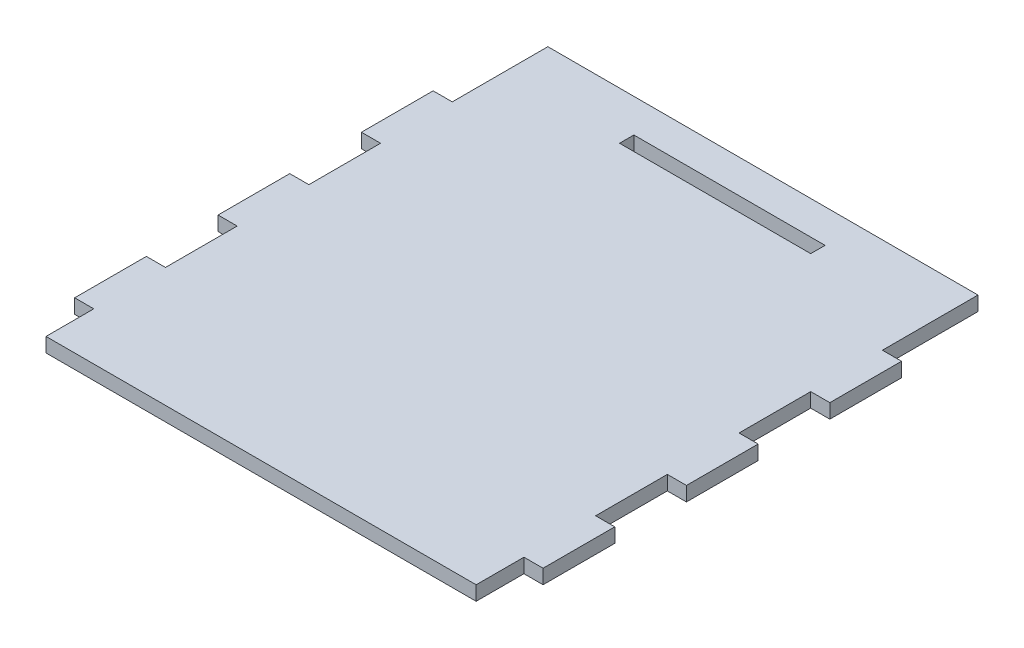
SolidWorks part; units mm, degrees
ref_plane "Front" through (0, 0, 0) normal (0, 0, 1) x (1, 0, 0)
ref_plane "Top" through (0, 0, 0) normal (0, 1, 0) x (1, 0, 0)
ref_plane "Right" through (0, 0, 0) normal (1, 0, 0) x (0, 0, -1)
sketch "Sketch1" plane through (0, 0, 0) normal (0, 1, 0) x (1, 0, 0)
  line L0 (0, 47.5) -> (90, 47.5) construction
  line L1 (0, 0) -> (90, 0)
  line L2 (0, 0) -> (0, 95)
  line L3 (0, 95) -> (90, 95)
  line L4 (90, 0) -> (90, 95)
  line L5 (45, 95) -> (45, 0) construction
  dimension "D1" = 90
  dimension "D7" = 95
extrude "Boss-Extrude1" add sketch "Sketch1" along normal blind 3
sketch "Sketch2" [suppressed] plane through (0, 3, 0) normal (0, 1, 0) x (1, 0, 0)
  line L1 (27.5, 98) -> (62.5, 98)
  line L2 (27.5, 98) -> (27.5, 95)
  line L3 (27.5, 95) -> (62.5, 95)
  line L4 (62.5, 98) -> (62.5, 95)
  dimension "D1" = 3
  dimension "D2" = 35
extrude "Boss-Extrude2" [suppressed] add sketch "Sketch2" against normal blind 3
sketch "Sketch3" [suppressed] plane through (0, 3, 0) normal (0, 1, 0) x (1, 0, 0)
  line L1 (-4, 67.5) -> (0, 67.5)
  line L2 (-4, 67.5) -> (-4, 27.5)
  line L3 (-4, 27.5) -> (0, 27.5)
  line L4 (0, 67.5) -> (0, 27.5)
  line L5 (90, 27.5) -> (94, 27.5)
  line L6 (90, 27.5) -> (90, 67.5)
  line L7 (90, 67.5) -> (94, 67.5)
  line L8 (94, 27.5) -> (94, 67.5)
  dimension "D1" = 40
  dimension "D2" = 4
  dimension "D3" = 4
extrude "Boss-Extrude3" [suppressed] add sketch "Sketch3" against normal blind 3
sketch "Sketch4" plane through (0, 3, 0) normal (0, 1, 0) x (1, 0, 0)
  line L0 (0, 0) -> (0, 95) construction
  line L1 (-4, 85) -> (0, 85)
  line L2 (-4, 85) -> (-4, 70)
  line L3 (-4, 70) -> (0, 70)
  line L4 (0, 85) -> (0, 70)
  line L5 (-4, 55) -> (0, 55)
  line L6 (-4, 55) -> (-4, 40)
  line L7 (-4, 40) -> (0, 40)
  line L8 (0, 55) -> (0, 40)
  line L9 (-4, 25) -> (0, 25)
  line L10 (-4, 25) -> (-4, 10)
  line L11 (-4, 10) -> (0, 10)
  line L12 (0, 25) -> (0, 10)
  line L13 (90, 85) -> (94, 85)
  line L14 (90, 85) -> (90, 70)
  line L15 (90, 70) -> (94, 70)
  line L16 (94, 85) -> (94, 70)
  line L17 (90, 55) -> (94, 55)
  line L18 (90, 55) -> (90, 40)
  line L19 (90, 40) -> (94, 40)
  line L20 (94, 55) -> (94, 40)
  line L21 (90, 25) -> (94, 25)
  line L22 (90, 25) -> (90, 10)
  line L23 (90, 10) -> (94, 10)
  line L24 (94, 25) -> (94, 10)
  line L25 (90, 0) -> (90, 95) construction
  line L26 (0, 0) -> (90, 0) construction
  line L28 (0, 95) -> (90, 95) construction
  line L29 (45, 95) -> (45, 0) construction
  point P34 (-4, 47.5)
  point P35 (45, 47.5)
  dimension "D2" = 4
  dimension "D1" = 4
  dimension "D3" = 15
  dimension "D4" = 15
  dimension "D5" = 15
  dimension "D6" = 10
  dimension "D7" = 95
  dimension "D8" = 10
extrude "Boss-Extrude4" add sketch "Sketch4" against normal blind 3
sketch "Sketch5" plane through (0, 3, 0) normal (0, 1, 0) x (1, 0, 0)
  line L1 (0, 105) -> (90, 105)
  line L2 (0, 105) -> (0, 95)
  line L3 (0, 95) -> (90, 95)
  line L4 (90, 105) -> (90, 95)
  dimension "D1" = 10
extrude "Boss-Extrude5" add sketch "Sketch5" against normal blind 3
sketch "Sketch6" plane through (0, 3, 0) normal (0, 1, 0) x (1, 0, 0)
  line L1 (25, 98) -> (65, 98)
  line L2 (25, 98) -> (25, 95)
  line L3 (25, 95) -> (65, 95)
  line L4 (65, 98) -> (65, 95)
  line L5 (0, 0) -> (90, 0) construction
  point P4 (45, 98)
  dimension "D1" = 3
  dimension "D2" = 40
  dimension "D3" = 95
extrude "Cut-Extrude2" cut sketch "Sketch6" against normal blind 4
equation "\"D3@Sketch3\"=\"D2@Sketch3\""
equation "\"D2@Sketch4\"=\"D1@Sketch4\""
equation "\"D4@Sketch4\"=\"D5@Sketch4\""
equation "\"D3@Sketch4\"=\"D5@Sketch4\""
